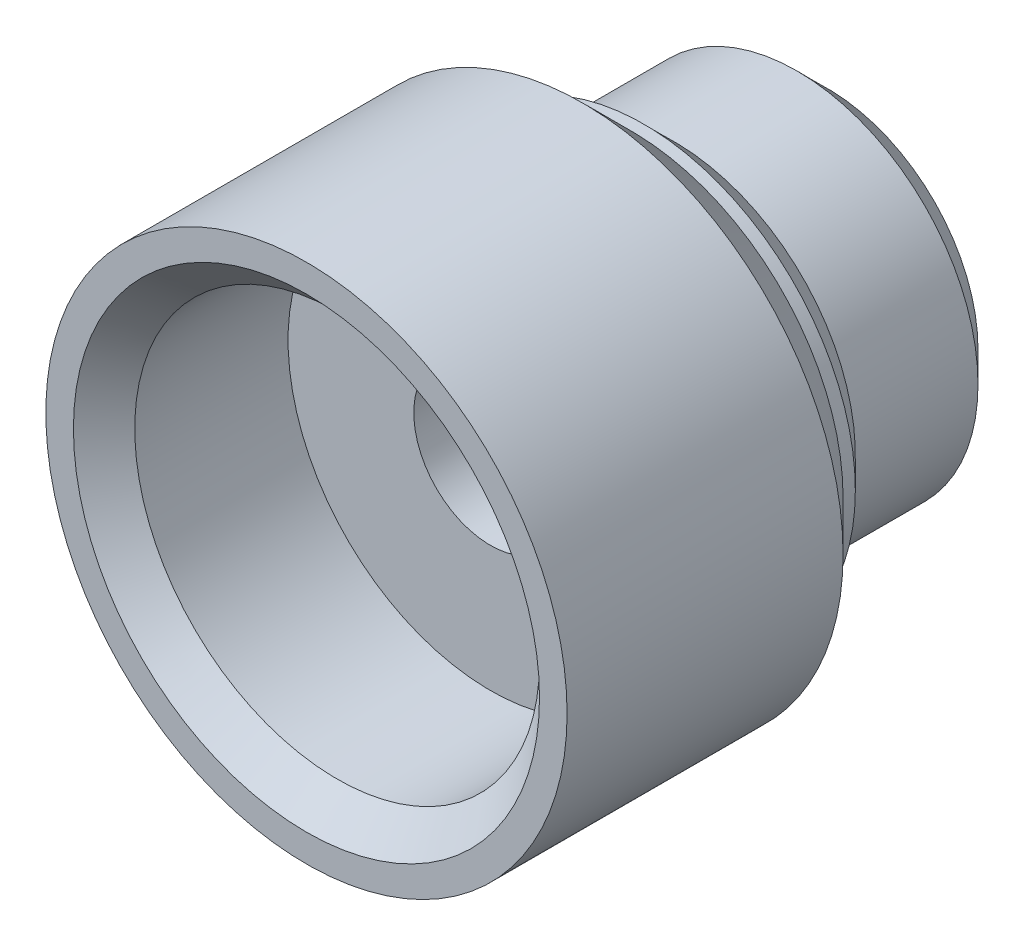
SolidWorks part; units mm, degrees
ref_plane "Front Plane" through (0, 0, 0) normal (0, 0, 1) x (1, 0, 0)
ref_plane "Top Plane" through (0, 0, 0) normal (0, 1, 0) x (1, 0, 0)
ref_plane "Right Plane" through (0, 0, 0) normal (1, 0, 0) x (0, 0, -1)
sketch "Sketch1" plane through (0, 0, 0) normal (0, 0, 1) x (1, 0, 0)
  circle A0 centre (0, 0) radius 2.95
  circle A1 centre (0, 0) radius 1.25
  dimension "D1" = 5.9
  dimension "D2" = 2.5
extrude "Boss-Extrude1" add sketch "Sketch1" along normal blind 3
sketch "Sketch2" plane through (0, 0, 3) normal (0, 0, 1) x (1, 0, 0)
  circle A0 centre (0, 0) radius 1.25
  circle A1 centre (0, 0) radius 4.25
  circle A2 centre (0, 0) radius 1.25 construction
  dimension "D1" = 8.5
extrude "Boss-Extrude2" add sketch "Sketch2" along normal blind 5.5
sketch "Sketch3" plane through (0, 0, 8.5) normal (0, 0, 1) x (1, 0, 0)
  circle A0 centre (0, 0) radius 3.3
  dimension "D1" = 6.6
extrude "Cut-Extrude1" cut sketch "Sketch3" against normal blind 3
chamfer "Chamfer1" distance 0.5 angle 45 1 edges at (3.3, 0, 8.5)
chamfer "Chamfer2" distance 0.5 angle 45 1 edges at (2.95, 0, 0)
sketch "Sketch4" plane through (0, 0, 3) normal (0, 0, -1) x (-1, 0, 0)
  circle A0 centre (0, 0) radius 1.25
  circle A1 centre (0, 0) radius 3.45
  circle A2 centre (0, 0) radius 1.25 construction
  circle A3 centre (0, 0) radius 2.95 construction
  dimension "D1" = 0.5
extrude "Boss-Extrude3" add sketch "Sketch4" along normal blind 0.5
chamfer "Chamfer3" distance 1 angle 45 1 edges at (4.25, 0, 3)
chamfer "Chamfer4" distance 0.5 angle 45 1 edges at (1.25, 0, 0)
chamfer "Chamfer6" distance 0.5 angle 45 1 edges at (-3.45, 0, 2.5)
